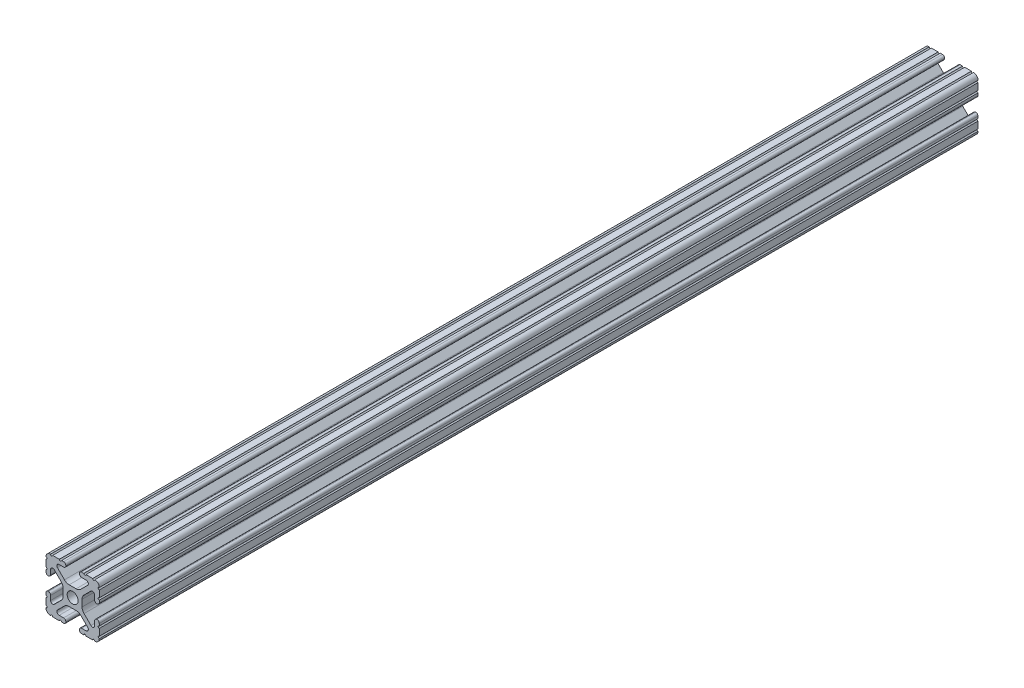
SolidWorks part; units mm, degrees
material "McMaster 6105-T5"
ref_plane "Front Plane" through (0, 0, 0) normal (0, 0, 1) x (1, 0, 0)
ref_plane "Top Plane" through (0, 0, 0) normal (0, 1, 0) x (1, 0, 0)
ref_plane "Right Plane" through (0, 0, 0) normal (1, 0, 0) x (0, 0, -1)
sketch "Sketch1" plane through (0, 0, 0) normal (0, 0, 1) x (1, 0, 0)
  line L88 (-7.1797, -8.6452) -> (-3.9523, -5.4237)
  line L89 (-1.7093, -4.4958) -> (1.7093, -4.4958)
  line L90 (3.9523, -5.4237) -> (7.1797, -8.6452)
  line L91 (6.4164, -10.4902) -> (4.2875, -10.4902)
  line L92 (3.2385, -11.5392) -> (3.2385, -11.651)
  line L93 (4.2875, -12.7) -> (5.3171, -12.7)
  line L94 (6.3331, -12.7) -> (9.5504, -12.7)
  line L95 (12.7, -9.5504) -> (12.7, -6.3331)
  line L96 (12.7, -5.3171) -> (12.7, -4.2875)
  line L97 (11.651, -3.2385) -> (11.5392, -3.2385)
  line L98 (10.4902, -4.2875) -> (10.4902, -6.4021)
  line L99 (8.7371, -7.1294) -> (5.441, -3.8408)
  line L100 (4.5085, -1.5932) -> (4.5085, 1.5932)
  line L101 (5.441, 3.8408) -> (8.7371, 7.1294)
  line L102 (10.4902, 6.4021) -> (10.4902, 4.2875)
  line L103 (11.5392, 3.2385) -> (11.651, 3.2385)
  line L104 (12.7, 4.2875) -> (12.7, 5.3171)
  line L105 (12.7, 6.3331) -> (12.7, 9.5504)
  line L106 (9.5504, 12.7) -> (6.3331, 12.7)
  line L107 (5.3171, 12.7) -> (4.2875, 12.7)
  line L108 (3.2385, 11.651) -> (3.2385, 11.5392)
  line L109 (4.2875, 10.4902) -> (6.4768, 10.4902)
  line L110 (7.207, 8.7244) -> (3.8983, 5.4232)
  line L111 (1.6558, 4.4958) -> (-1.6558, 4.4958)
  line L112 (-3.8983, 5.4232) -> (-7.207, 8.7244)
  line L113 (-6.4768, 10.4902) -> (-4.2875, 10.4902)
  line L114 (-3.2385, 11.5392) -> (-3.2385, 11.651)
  line L115 (-4.2875, 12.7) -> (-5.3171, 12.7)
  line L116 (-6.3331, 12.7) -> (-9.5504, 12.7)
  line L117 (-12.7, 9.5504) -> (-12.7, 6.3331)
  line L118 (-12.7, 5.3171) -> (-12.7, 4.2875)
  line L119 (-11.651, 3.2385) -> (-11.5392, 3.2385)
  line L120 (-10.4902, 4.2875) -> (-10.4902, 6.4021)
  line L121 (-8.7371, 7.1294) -> (-5.441, 3.8408)
  line L122 (-4.5085, 1.5932) -> (-4.5085, -1.5932)
  line L123 (-5.441, -3.8408) -> (-8.7371, -7.1294)
  line L124 (-10.4902, -6.4021) -> (-10.4902, -4.2875)
  line L125 (-11.5392, -3.2385) -> (-11.651, -3.2385)
  line L126 (-12.7, -4.2875) -> (-12.7, -5.3171)
  line L127 (-12.7, -6.3331) -> (-12.7, -9.5504)
  line L128 (-9.5504, -12.7) -> (-6.3331, -12.7)
  line L129 (-5.3171, -12.7) -> (-4.2875, -12.7)
  line L130 (-3.2385, -11.651) -> (-3.2385, -11.5392)
  line L131 (-4.2875, -10.4902) -> (-6.4164, -10.4902)
  circle A1 centre (0, 0) radius 2.6035
  arc A104 (-7.1797, -8.6452) -> (-6.4164, -10.4902) centre (-6.4164, -9.4098) ccw
  arc A105 (-1.7093, -4.4958) -> (-3.9523, -5.4237) centre (-1.7093, -7.6708) ccw
  arc A106 (3.9523, -5.4237) -> (1.7093, -4.4958) centre (1.7093, -7.6708) ccw
  arc A107 (6.4164, -10.4902) -> (7.1797, -8.6452) centre (6.4164, -9.4098) ccw
  arc A108 (4.2875, -10.4902) -> (3.2385, -11.5392) centre (4.2875, -11.5392) ccw
  arc A109 (3.2385, -11.651) -> (4.2875, -12.7) centre (4.2875, -11.651) ccw
  arc A110 (6.3331, -12.7) -> (5.3171, -12.7) centre (5.8251, -12.7) ccw
  arc A111 (10.5664, -12.6998) -> (9.5504, -12.7) centre (10.0584, -12.7) ccw
  arc A112 (10.5664, -12.6998) -> (12.6998, -10.5664) centre (10.5918, -10.5918) ccw
  arc A113 (12.7, -9.5504) -> (12.6998, -10.5664) centre (12.7, -10.0584) ccw
  arc A114 (12.7, -5.3171) -> (12.7, -6.3331) centre (12.7, -5.8251) ccw
  arc A115 (12.7, -4.2875) -> (11.651, -3.2385) centre (11.651, -4.2875) ccw
  arc A116 (11.5392, -3.2385) -> (10.4902, -4.2875) centre (11.5392, -4.2875) ccw
  arc A117 (8.7371, -7.1294) -> (10.4902, -6.4021) centre (9.4628, -6.4021) ccw
  arc A118 (4.5085, -1.5932) -> (5.441, -3.8408) centre (7.6835, -1.5932) ccw
  arc A119 (5.441, 3.8408) -> (4.5085, 1.5932) centre (7.6835, 1.5932) ccw
  arc A120 (10.4902, 6.4021) -> (8.7371, 7.1294) centre (9.4628, 6.4021) ccw
  arc A121 (10.4902, 4.2875) -> (11.5392, 3.2385) centre (11.5392, 4.2875) ccw
  arc A122 (11.651, 3.2385) -> (12.7, 4.2875) centre (11.651, 4.2875) ccw
  arc A123 (12.7, 6.3331) -> (12.7, 5.3171) centre (12.7, 5.8251) ccw
  arc A124 (12.6998, 10.5664) -> (12.7, 9.5504) centre (12.7, 10.0584) ccw
  arc A125 (12.6998, 10.5664) -> (10.5664, 12.6998) centre (10.5918, 10.5918) ccw
  arc A126 (9.5504, 12.7) -> (10.5664, 12.6998) centre (10.0584, 12.7) ccw
  arc A127 (5.3171, 12.7) -> (6.3331, 12.7) centre (5.8251, 12.7) ccw
  arc A128 (4.2875, 12.7) -> (3.2385, 11.651) centre (4.2875, 11.651) ccw
  arc A129 (3.2385, 11.5392) -> (4.2875, 10.4902) centre (4.2875, 11.5392) ccw
  arc A130 (7.207, 8.7244) -> (6.4768, 10.4902) centre (6.4768, 9.4563) ccw
  arc A131 (1.6558, 4.4958) -> (3.8983, 5.4232) centre (1.6558, 7.6708) ccw
  arc A132 (-3.8983, 5.4232) -> (-1.6558, 4.4958) centre (-1.6558, 7.6708) ccw
  arc A133 (-6.4768, 10.4902) -> (-7.207, 8.7244) centre (-6.4768, 9.4563) ccw
  arc A134 (-4.2875, 10.4902) -> (-3.2385, 11.5392) centre (-4.2875, 11.5392) ccw
  arc A135 (-3.2385, 11.651) -> (-4.2875, 12.7) centre (-4.2875, 11.651) ccw
  arc A136 (-6.3331, 12.7) -> (-5.3171, 12.7) centre (-5.8251, 12.7) ccw
  arc A137 (-10.5664, 12.6998) -> (-9.5504, 12.7) centre (-10.0584, 12.7) ccw
  arc A138 (-10.5664, 12.6998) -> (-12.6998, 10.5664) centre (-10.5918, 10.5918) ccw
  arc A139 (-12.7, 9.5504) -> (-12.6998, 10.5664) centre (-12.7, 10.0584) ccw
  arc A140 (-12.7, 5.3171) -> (-12.7, 6.3331) centre (-12.7, 5.8251) ccw
  arc A141 (-12.7, 4.2875) -> (-11.651, 3.2385) centre (-11.651, 4.2875) ccw
  arc A142 (-11.5392, 3.2385) -> (-10.4902, 4.2875) centre (-11.5392, 4.2875) ccw
  arc A143 (-8.7371, 7.1294) -> (-10.4902, 6.4021) centre (-9.4628, 6.4021) ccw
  arc A144 (-4.5085, 1.5932) -> (-5.441, 3.8408) centre (-7.6835, 1.5932) ccw
  arc A145 (-5.441, -3.8408) -> (-4.5085, -1.5932) centre (-7.6835, -1.5932) ccw
  arc A146 (-10.4902, -6.4021) -> (-8.7371, -7.1294) centre (-9.4628, -6.4021) ccw
  arc A147 (-10.4902, -4.2875) -> (-11.5392, -3.2385) centre (-11.5392, -4.2875) ccw
  arc A148 (-11.651, -3.2385) -> (-12.7, -4.2875) centre (-11.651, -4.2875) ccw
  arc A149 (-12.7, -6.3331) -> (-12.7, -5.3171) centre (-12.7, -5.8251) ccw
  arc A150 (-12.6998, -10.5664) -> (-12.7, -9.5504) centre (-12.7, -10.0584) ccw
  arc A151 (-12.6998, -10.5664) -> (-10.5664, -12.6998) centre (-10.5918, -10.5918) ccw
  arc A152 (-9.5504, -12.7) -> (-10.5664, -12.6998) centre (-10.0584, -12.7) ccw
  arc A153 (-5.3171, -12.7) -> (-6.3331, -12.7) centre (-5.8251, -12.7) ccw
  arc A154 (-4.2875, -12.7) -> (-3.2385, -11.651) centre (-4.2875, -11.651) ccw
  arc A155 (-3.2385, -11.5392) -> (-4.2875, -10.4902) centre (-4.2875, -11.5392) ccw
extrude "Boss-Extrude1" add sketch "Sketch1" along normal mid plane 419.1
sketch "Sketch2" plane through (0, 12.7, 0) normal (0, 1, 0) x (1, 0, 0)
  line L0 (0, -155.4789) -> (0, 151.1822) construction
  line L1 (1.6558, -209.55) -> (-1.6558, -209.55) construction
  line L2 (1.6558, 209.55) -> (-1.6558, 209.55) construction
  circle A0 centre (0, -146.05) radius 3.175
  circle A1 centre (0, 184.15) radius 3.175
  point P4 (0, -209.55)
  point P12 (0, 209.55)
  dimension "D3" = 6.35
  dimension "D1" = 63.5
  dimension "D2" = 25.4
extrude "Cut-Extrude1" [suppressed] cut sketch "Sketch2" against normal through all both and the other way through all
sketch "Sketch3" plane through (-12.7, 0, 0) normal (-1, 0, 0) x (0, 0, 1)
  line L0 (-144.1574, 0) -> (-126.6701, 0) construction
  line L2 (209.55, 1.5932) -> (209.55, -1.5932) construction
  line L3 (-209.55, 1.5932) -> (-209.55, -1.5932) construction
  circle A0 centre (-158.75, 0) radius 3.175
  circle A1 centre (-133.35, 0) radius 3.175
  dimension "D1" = 6.35
  dimension "D2" = 342.9
  dimension "D3" = 50.8
extrude "Cut-Extrude2" [suppressed] cut sketch "Sketch3" against normal through all both and the other way through all
